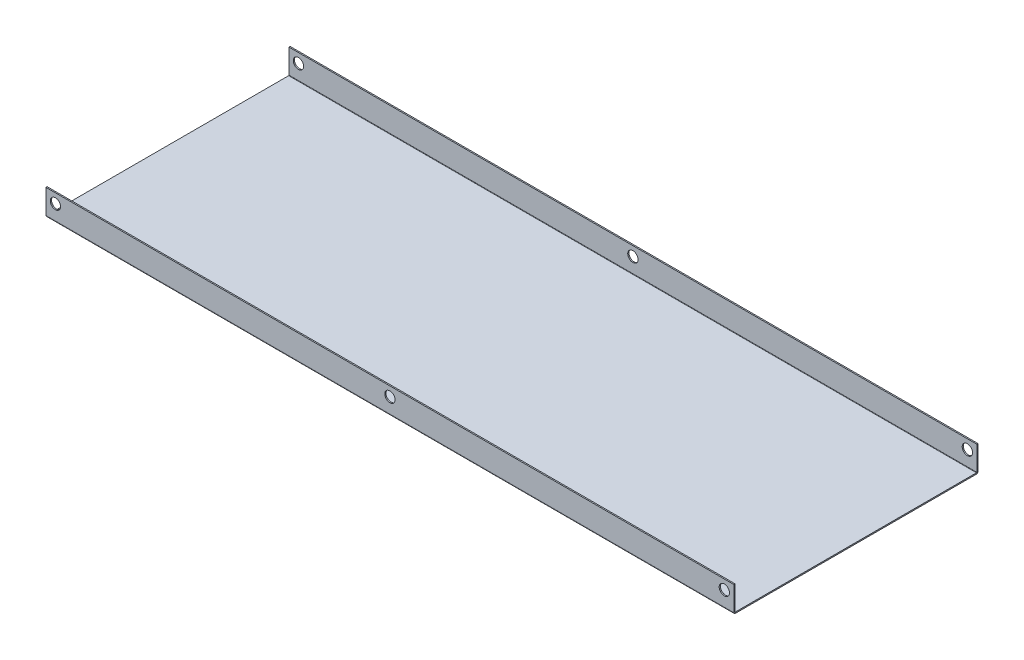
SolidWorks part; units mm, degrees
note: The reader was unsure of these and kept them because the rebuilt part matched: thickness of "基体-法兰1", "边线-法兰1", "钣金8", "钣金9", "钣金10", "钣金11"; flange length of "边线-法兰1".
material "1023 碳钢板 (SS)"
ref_plane "前视基准面" through (0, 0, 0) normal (0, 0, 1) x (1, 0, 0)
ref_plane "上视基准面" through (0, 0, 0) normal (0, 1, 0) x (1, 0, 0)
ref_plane "右视基准面" through (0, 0, 0) normal (1, 0, 0) x (0, 0, -1)
sketch "草图1" plane through (0, 0, 0) normal (0, 1, 0) x (1, 0, 0)
  line L1 (-200, -71) -> (200, -71)
  line L2 (-200, -71) -> (-200, 71)
  line L3 (-200, 71) -> (200, 71)
  line L4 (200, -71) -> (200, 71)
  line L5 (-200, -71) -> (200, 71) construction
  line L6 (-200, 71) -> (200, -71) construction
  point P0 (0, 0)
  dimension "D1" = 142
  dimension "D2" = 400
base flange "基体-法兰1" sketch "草图1" thickness 0.7 reverse thickness direction no parameters "D1"=0.2
edge flange "边线-法兰1" sketch "草图15" flange profiles "草图15", "草图16" flange angle 90 flange length 15 flange position material inside bend radius 0.2 thickness 0.7 relief rectangular parameters "D6"=10, "D8"=1
sketch "草图15" plane through (0, 0, -71) normal (0, 0, -1) x (-1, 0, 0)
  line L2 (-200, 0) -> (-200, 14.3)
  line L3 (-200, 14.3) -> (200, 14.3)
  line L4 (200, 14.3) -> (200, 0)
  line L11 (-200, 0) -> (200, 0) construction
  line L12 (-200, 0) -> (200, 0)
sketch "草图16" plane through (0, 0, 71) normal (0, 0, 1) x (1, 0, 0)
  line L2 (-200, 0) -> (-200, 14.3)
  line L3 (-200, 14.3) -> (200, 14.3)
  line L4 (200, 14.3) -> (200, 0)
  line L7 (-200, 0) -> (200, 0) construction
  line L8 (-200, 0) -> (200, 0)
bend "边线折弯1" bend radius 0.2 bend angle 90 parameters "D5"=1
bend "边线折弯2" bend radius 0.2 bend angle 90 parameters "D5"=2
sketch "草图17" plane through (0, 0, -71) normal (0, 0, -1) x (-1, 0, 0)
  line L0 (200, 14.3) -> (-200, 14.3) construction
  line L1 (-200, 14.3) -> (-200, 0.2) construction
  line L2 (0, 14.3) -> (0, 0) construction
  circle A0 centre (-194.5, 8.8) radius 3
  circle A1 centre (0, 8.8) radius 3
  circle A2 centre (194.5, 8.8) radius 3
  dimension "D1" = 5.5
  dimension "D2" = 5.5
  dimension "D3" = 6
  dimension "D4" = 5.5
  dimension "D5" = 6
extrude "切除-拉伸1" cut sketch "草图17" against normal blind 10
sketch "草图18" plane through (0, 0, 71) normal (0, 0, 1) x (1, 0, 0)
  line L0 (200, 14.3) -> (-200, 14.3) construction
  line L1 (-200, 14.3) -> (-200, 0.2) construction
  line L2 (0, 14.3) -> (0, 0) construction
  circle A0 centre (-194.5, 8.8) radius 3
  circle A1 centre (0, 8.8) radius 3
  circle A2 centre (194.5, 8.8) radius 3
  dimension "D1" = 5.5
  dimension "D2" = 5.5
  dimension "D3" = 5.5
  dimension "D4" = 6
  dimension "D5" = 6
extrude "切除-拉伸2" cut sketch "草图18" against normal blind 10
sketch "折弯-线3" plane through (0, 0, 0) normal (0, 1, 0) x (1, 0, 0)
sketch "边界框3" plane through (0, 0, 0) normal (0, 1, 0) x (1, 0, 0)
sheet metal parameters "钣金8" thickness 0.7 parameters "D1"=0.2
flat pattern "平板型式8" [suppressed]
sketch "折弯-线4" plane through (0, 0, 0) normal (0, 1, 0) x (1, 0, 0)
sketch "边界框4" [suppressed] plane through (0, 0, 0) normal (0, 1, 0) x (1, 0, 0)
sheet metal parameters "钣金9" thickness 0.7 parameters "D1"=0.2, "D7"=0.01
flat pattern "平板型式8" [suppressed]
sketch "折弯-线4" plane through (0, 0, 0) normal (0, 1, 0) x (1, 0, 0)
sketch "边界框4" [suppressed] plane through (0, 0, 0) normal (0, 1, 0) x (1, 0, 0)
bend of the flat pattern "展平-<边线折弯1>1"
bend of the flat pattern "展平-<边线折弯2>1"
sheet metal parameters "钣金10" thickness 0.7 parameters "D1"=0.2, "D7"=0.01
flat pattern "平板型式8" [suppressed]
sketch "折弯-线4" plane through (0, 0, 0) normal (0, 1, 0) x (1, 0, 0)
sketch "边界框4" [suppressed] plane through (0, 0, 0) normal (0, 1, 0) x (1, 0, 0)
bend of the flat pattern "展平-<边线折弯1>1"
bend of the flat pattern "展平-<边线折弯2>1"
sheet metal parameters "钣金11" thickness 0.7 parameters "D1"=0.2, "D7"=0.01
flat pattern "平板型式8" [suppressed]
sketch "折弯-线4" plane through (0, 0, 0) normal (0, 1, 0) x (1, 0, 0)
sketch "边界框4" [suppressed] plane through (0, 0, 0) normal (0, 1, 0) x (1, 0, 0)
bend of the flat pattern "展平-<边线折弯1>1"
bend of the flat pattern "展平-<边线折弯2>1"
